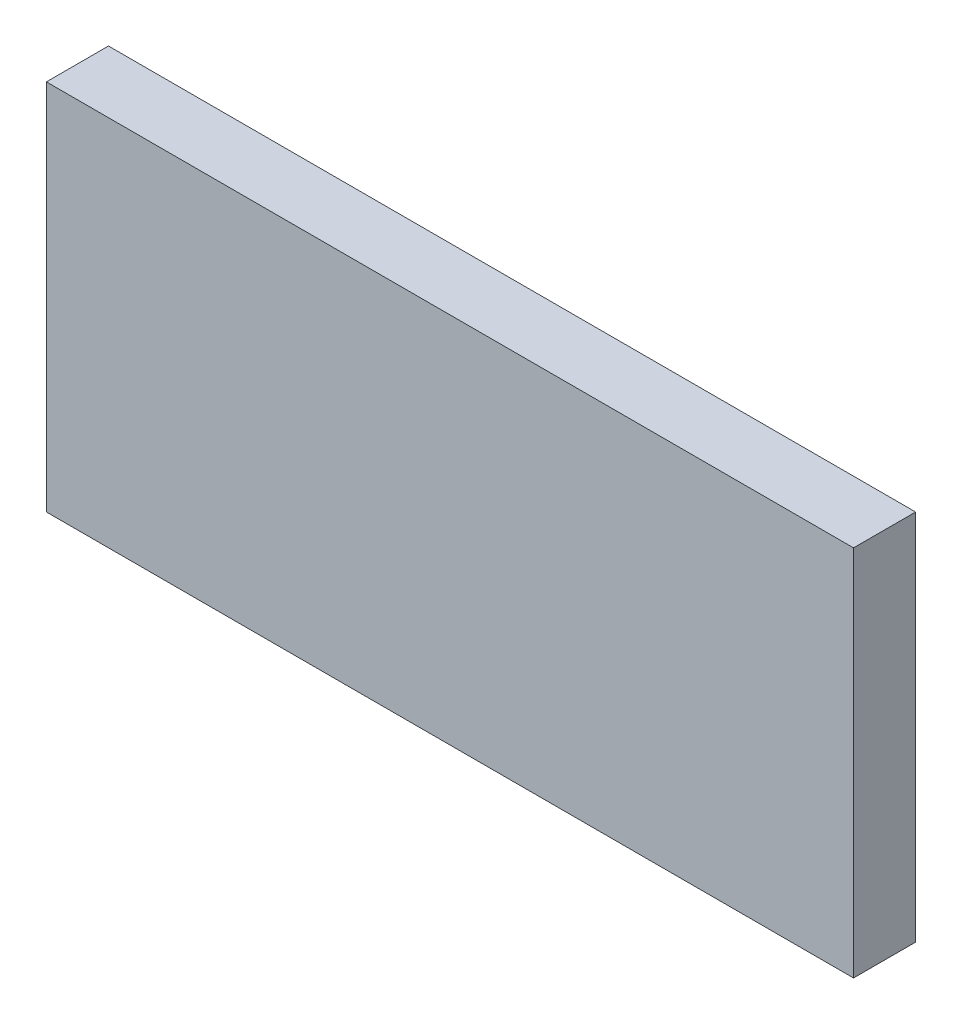
SolidWorks part; units mm, degrees
material "201 Annealed Stainless Steel (SS)"
ref_plane "Front Plane" through (0, 0, 0) normal (0, 0, 1) x (1, 0, 0)
ref_plane "Top Plane" through (0, 0, 0) normal (0, 1, 0) x (1, 0, 0)
ref_plane "Right Plane" through (0, 0, 0) normal (1, 0, 0) x (0, 0, -1)
sketch "Sketch1" plane through (0, 0, 0) normal (0, 0, 1) x (1, 0, 0)
  line L1 (-32.5, -15) -> (32.5, -15)
  line L2 (-32.5, -15) -> (-32.5, 15)
  line L3 (-32.5, 15) -> (32.5, 15)
  line L4 (32.5, -15) -> (32.5, 15)
  line L5 (-32.5, -15) -> (32.5, 15) construction
  line L6 (-32.5, 15) -> (32.5, -15) construction
  point P0 (0, 0)
  dimension "D1" = 65
  dimension "D2" = 30
extrude "Boss-Extrude1" add sketch "Sketch1" along normal blind 5
sketch "Sketch2" [suppressed] plane through (0, 0, 0) normal (0, 0, -1) x (-1, 0, 0)
  line L0 (61, 200) -> (61, -200) construction
  line L1 (-61, 314.7216) -> (-204.3993, 314.7216)
  line L2 (-61, 314.7216) -> (-61, -251.9618)
  line L3 (-61, -251.9618) -> (-204.3993, -251.9618)
  line L4 (-204.3993, 314.7216) -> (-204.3993, -251.9618)
  line L6 (61, 279.3211) -> (244.4765, 279.3211)
  line L7 (61, 279.3211) -> (61, -295.1839)
  line L8 (61, -295.1839) -> (244.4765, -295.1839)
  line L9 (244.4765, 279.3211) -> (244.4765, -295.1839)
  line L10 (-61, -200) -> (-61, -140) construction
extrude "Cut-Extrude1" [suppressed] cut sketch "Sketch2" against normal through all
sketch "Sketch3" [suppressed] plane through (49, 0, 0) normal (1, 0, 0) x (0, 0, -1)
  circle A0 centre (-6.722, 55.3681) radius 5.3835
surface "Surface-Extrude1" [suppressed] sketch "Sketch3"
sketch "Sketch4" [suppressed] plane through (-49, 0, 0) normal (-1, 0, 0) x (0, 0, 1)
  line L1 (2, 80) -> (0, 80) construction
  line L2 (0, -80) -> (0, 80) construction
  point P0 (7.5, 76)
  dimension "D1" = 4
  dimension "D2" = 7.5
ref_axis "Axis1" [suppressed] through (-49, 76, 7.5) along (1, 0, 0)
sketch "Sketch5" [suppressed] plane through (0, 0, 0) normal (0, 0, -1) x (-1, 0, 0)
  line L0 (49, 80) -> (49, -80) construction
  line L1 (-49, 80) -> (49, 80)
  line L2 (-49, 80) -> (-49, 60.2594)
  line L3 (-49, 60.2594) -> (49, 60.2594)
  line L4 (49, 80) -> (49, 60.2594)
extrude "Cut-Extrude2" [suppressed] cut sketch "Sketch5" against normal blind 3
sketch "Sketch6" [suppressed] plane through (0, 0, 2) normal (0, 0, 1) x (1, 0, 0)
  line L2 (0, -1.1) -> (0, 1.1) construction
  line L3 (-30, -15) -> (30, -15) construction
  circle A0 centre (0, -15) radius 20
  dimension "D1" = 40
extrude "Cut-Extrude3" [suppressed] cut sketch "Sketch6" against normal through all
